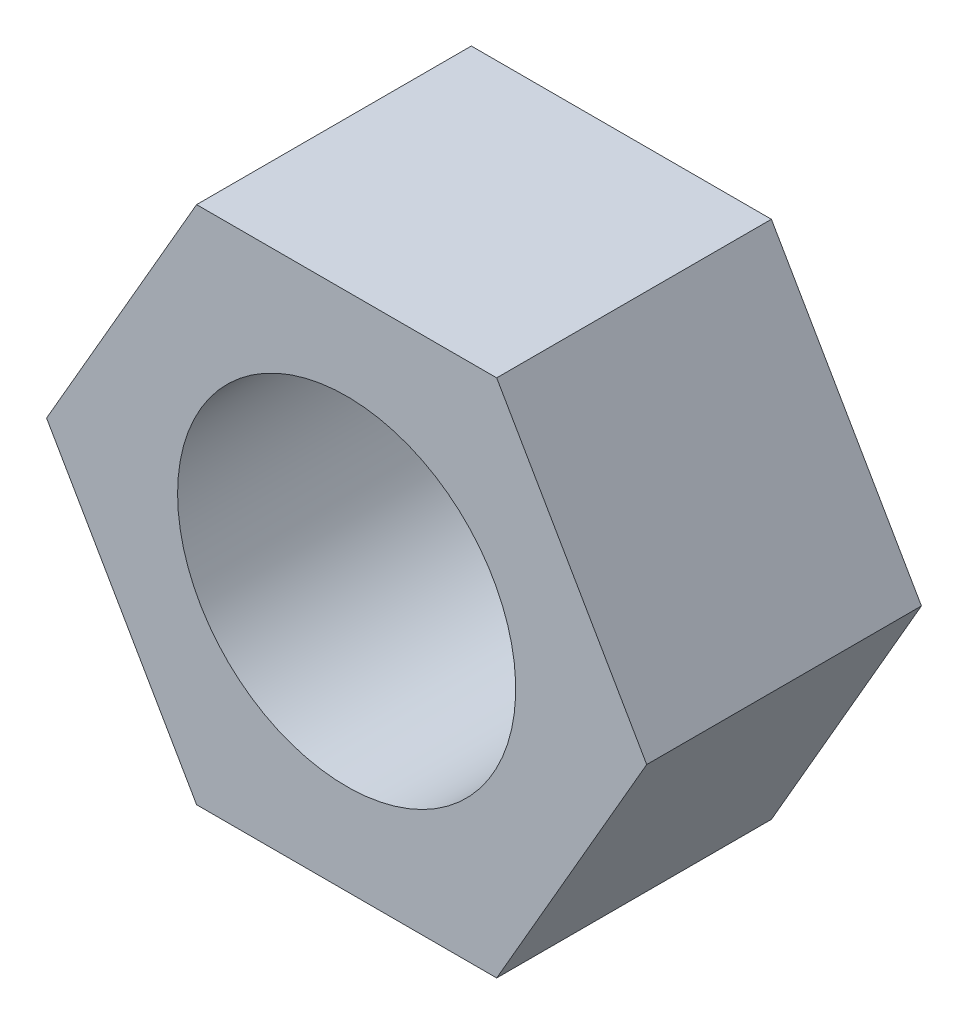
SolidWorks part; units mm, degrees
material "Plain Carbon Steel"
ref_plane "Спереди" through (0, 0, 0) normal (0, 0, 1) x (1, 0, 0)
ref_plane "Сверху" through (0, 0, 0) normal (0, 1, 0) x (1, 0, 0)
ref_plane "Справа" through (0, 0, 0) normal (1, 0, 0) x (0, 0, -1)
sketch "Sketch1" plane through (0, 0, 0) normal (0, 0, 1) x (1, 0, 0)
  line L1 (7.1, 0) -> (3.55, 6.1488)
  line L2 (3.55, 6.1488) -> (-3.55, 6.1488)
  line L3 (-3.55, 6.1488) -> (-7.1, 0)
  line L4 (-7.1, 0) -> (-3.55, -6.1488)
  line L5 (-3.55, -6.1488) -> (3.55, -6.1488)
  line L6 (3.55, -6.1488) -> (7.1, 0)
  circle A0 centre (0, 0) radius 6.1488 construction
  circle A1 centre (0, 0) radius 4
  dimension "D1" = 8
  dimension "D2" = 14.2
extrude "Boss-Extrude1" add sketch "Sketch1" along normal blind 6.5
